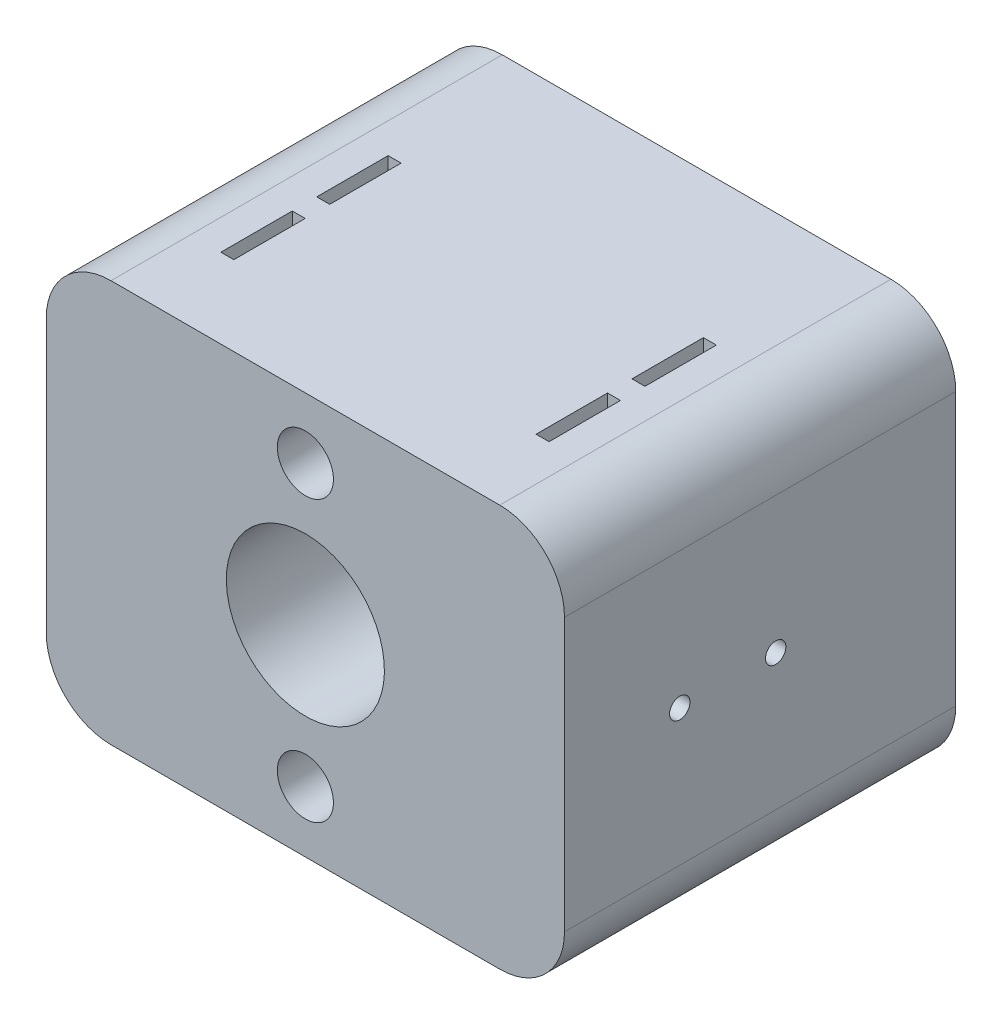
SolidWorks part; units mm, degrees
ref_plane "Front Plane" through (0, 0, 0) normal (0, 0, 1) x (1, 0, 0)
ref_plane "Top Plane" through (0, 0, 0) normal (0, 1, 0) x (1, 0, 0)
ref_plane "Right Plane" through (0, 0, 0) normal (1, 0, 0) x (0, 0, -1)
sketch "Sketch1" plane through (0, 0, 0) normal (0, 0, 1) x (1, 0, 0)
  line L0 (-82.55, -139.7) -> (-82.55, 139.7) construction
  line L1 (-82.55, 29.2453) -> (-31.75, 29.2453)
  line L2 (-82.55, 29.2453) -> (-82.55, -10.15)
  line L3 (-82.55, -10.15) -> (-31.75, -10.15)
  line L4 (-31.75, 29.2453) -> (-31.75, -10.15)
  line L5 (-82.55, 29.2453) -> (-31.75, -10.15) construction
  line L6 (-82.55, -10.15) -> (-31.75, 29.2453) construction
  line L7 (-31.75, -139.7) -> (-31.75, 139.7) construction
  arc A0 (-49.53, -8.6164) -> (-43.6698, -4.8149) centre (-57.15, 9.5476) ccw construction
  arc A1 (-64.77, 27.7117) -> (-70.6302, 23.9102) centre (-57.15, 9.5476) ccw construction
  circle A2 centre (-57.15, 23.27) radius 2.75
  circle A3 centre (-57.15, -4.1747) radius 2.75
  circle A4 centre (-57.15, -4.1747) radius 2.75 construction
  circle A5 centre (-57.15, 9.5476) radius 7.747
  circle A6 centre (-57.15, 9.5476) radius 7.747 construction
  point P4 (-57.15, 9.5476)
extrude "Boss-Extrude1" add sketch "Sketch1" along normal up to surface (38.35 mm away) contours L4 L1 L2 L3 A3 A2 region at (-57.15, 28.6025, 0)
sketch "Sketch2" plane through (0, -10.15, 0) normal (0, -1, 0) x (-1, 0, 0)
  line L5 (44.45, -17.65) -> (38.95, -17.65) construction
  line L6 (71.965, -14.15) -> (73.235, -14.15)
  line L7 (42.335, -30.55) -> (41.065, -30.55)
  line L8 (42.335, -30.55) -> (42.335, -23.55)
  line L9 (42.335, -23.55) -> (41.065, -23.55)
  line L10 (41.065, -30.55) -> (41.065, -23.55)
  line L11 (42.335, -30.55) -> (41.065, -23.55) construction
  line L12 (42.335, -23.55) -> (41.065, -30.55) construction
  line L17 (20.2, -30.55) -> (5.2, -30.55) construction
  line L20 (41.065, -14.15) -> (42.335, -14.15)
  line L21 (41.065, -14.15) -> (41.065, -21.15)
  line L22 (41.065, -21.15) -> (42.335, -21.15)
  line L23 (42.335, -14.15) -> (42.335, -21.15)
  line L24 (41.065, -14.15) -> (42.335, -21.15) construction
  line L25 (41.065, -21.15) -> (42.335, -14.15) construction
  line L30 (71.965, -14.15) -> (71.965, -21.15)
  line L31 (71.965, -21.15) -> (73.235, -21.15)
  line L32 (73.235, -14.15) -> (73.235, -21.15)
  line L33 (71.965, -14.15) -> (73.235, -21.15) construction
  line L34 (71.965, -21.15) -> (73.235, -14.15) construction
  line L35 (73.235, -23.55) -> (71.965, -23.55)
  line L36 (73.235, -23.55) -> (73.235, -30.55)
  line L37 (73.235, -30.55) -> (71.965, -30.55)
  line L38 (71.965, -23.55) -> (71.965, -30.55)
  line L39 (73.235, -23.55) -> (71.965, -30.55) construction
  line L40 (73.235, -30.55) -> (71.965, -23.55) construction
  line L41 (38.95, -6.35) -> (38.95, -22.35) construction
  line L42 (44.45, -22.35) -> (44.45, -6.35) construction
  line L43 (5.2, -14.15) -> (20.2, -14.15) construction
  line L45 (5.2, -23.55) -> (20.2, -23.55) construction
  line L46 (69.85, -27.05) -> (75.35, -27.05) construction
  line L47 (75.35, -32) -> (75.35, 3.175) construction
  line L48 (69.85, 3.175) -> (69.85, -32) construction
  point P4 (72.6, -17.65)
  point P9 (41.7, -27.05)
  point P14 (72.6, -27.05)
  point P15 (69.85, -27.05)
  point P21 (41.7, -17.65)
  point P31 (41.7, -17.65)
  point P41 (72.6, -27.05)
  dimension "D1" = 1.27
extrude "Cut-Extrude1" cut sketch "Sketch2" against normal through all both and the other way through all contours L10 L7 L8 L9 | L32 L6 L30 L31 | L35 L38 L37 L36 | L23 L22 L21 L20 region at (-72.6, -10.15, 17.65) region at (-41.7, -10.15, 27.05) region at (-72.6, -10.15, 27.05)
sketch "Sketch3" plane through (-31.75, 0, 0) normal (1, 0, 0) x (0, 0, -1)
  line L0 (-23.55, 9.5476) -> (-30.55, 9.5476) construction
  line L1 (-30.55, 29.2453) -> (-30.55, -10.15) construction
  line L3 (-23.55, 29.2453) -> (-23.55, -10.15) construction
  line L4 (-38.35, -10.15) -> (-38.35, 29.2453) construction
  line L8 (-14.15, 29.2453) -> (-21.15, 29.2453) construction
  circle A0 centre (-27.05, 9.5476) radius 3.5
  circle A1 centre (-17.65, 9.5476) radius 1
  circle A3 centre (-27.05, 9.5476) radius 1
  point P7 (-27.05, 9.5476)
  point P10 (-19.0238, 9.5476)
  point P17 (-38.35, 9.5476)
  point P18 (-17.65, 29.2453)
  dimension "D1" = 2
extrude "Cut-Extrude2" cut sketch "Sketch3" against normal through all both and the other way through all contours A3 | A1
fillet "Fillet1" radius 6.35 4 edges at (-82.55, -10.15, 19.175) (-82.55, 29.2453, 19.175) (-31.75, -10.15, 19.175) (-31.75, 29.2453, 19.175)
